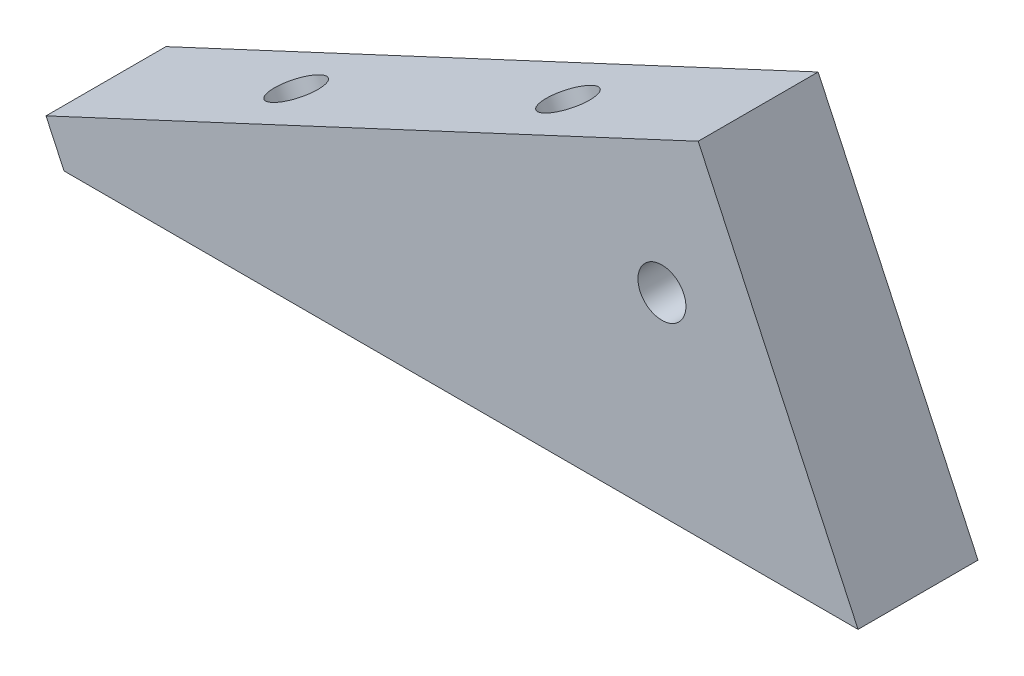
SolidWorks part; units mm, degrees
ref_plane "Front Plane" through (0, 0, 0) normal (0, 0, 1) x (1, 0, 0)
ref_plane "Top Plane" through (0, 0, 0) normal (0, 1, 0) x (1, 0, 0)
ref_plane "Right Plane" through (0, 0, 0) normal (1, 0, 0) x (0, 0, -1)
sketch "Sketch1" plane through (0, 0, 0) normal (0, 0, 1) x (1, 0, 0)
  line L0 (121.4984, 0.0035) -> (108.169, 28.5884)
  line L1 (-85.1981, -61.5801) -> (277.3251, 107.4672) construction
  line L2 (108.169, 28.5884) -> (53.7905, 3.2313)
  line L3 (53.7905, 3.2313) -> (55.2957, 0.0035)
  line L4 (55.2957, 0.0035) -> (121.4984, 0.0035)
  dimension "D1" = 60
  dimension "D2" = 31.54
extrude "Boss-Extrude1" add sketch "Sketch1" against normal blind 10
sketch "Sketch2" plane through (8.3697, -17.9488, 0) normal (-0.4226, 0.9063, 0) x (0.9063, 0.4226, 0)
  line L0 (50.1164, 5) -> (110.1164, 5) construction
  line L1 (50.1164, 10) -> (50.1164, 0) construction
  line L2 (110.1164, 10) -> (110.1164, 0) construction
  line L3 (80.1164, 10) -> (80.1164, 0) construction
  line L4 (92.6164, 0.9585) -> (96.1164, 2.9793)
  line L5 (96.1164, 2.9793) -> (96.1164, 7.0207)
  line L6 (96.1164, 7.0207) -> (92.6164, 9.0415)
  line L7 (92.6164, 9.0415) -> (89.1164, 7.0207)
  line L8 (89.1164, 7.0207) -> (89.1164, 2.9793)
  line L9 (89.1164, 2.9793) -> (92.6164, 0.9585)
  line L10 (110.1164, 10) -> (50.1164, 10) construction
  line L11 (110.1164, 0) -> (50.1164, 0) construction
  line L12 (71.1164, 2.9793) -> (67.6164, 0.9585)
  line L13 (67.6164, 0.9585) -> (64.1164, 2.9793)
  line L14 (71.1164, 7.0207) -> (71.1164, 2.9793)
  line L15 (67.6164, 9.0415) -> (71.1164, 7.0207)
  line L16 (64.1164, 7.0207) -> (67.6164, 9.0415)
  line L17 (64.1164, 2.9793) -> (64.1164, 7.0207)
  circle A0 centre (92.6164, 5) radius 3.5 construction
  circle A1 centre (92.6164, 5) radius 2
  circle A2 centre (67.6164, 5) radius 3.5 construction
  circle A3 centre (67.6164, 5) radius 2
  dimension "D3" = 4
  dimension "D1" = 17.5
  dimension "D2" = 7
extrude "Cut-Extrude1" cut sketch "Sketch2" against normal through all contours A3 | A1 region at (92.3086, 21.1926, -5) region at (69.6509, 10.6271, -5)
extrude "Cut-Extrude2" cut sketch "Sketch2<3>" against normal through all from offset 4 offset against normal yes
sketch "Sketch2<3>" plane through (8.3697, -17.9488, 0) normal (-0.4226, 0.9063, 0) x (0.9063, 0.4226, 0) same geometry as "Sketch2"
sketch "Sketch3" plane through (0, 0.0035, 0) normal (0, -1, 0) x (1, 0, 0)
  line L0 (121.4984, -5) -> (55.2957, -5) construction
  line L1 (121.4984, -10) -> (121.4984, 0) construction
  line L2 (55.2957, -10) -> (55.2957, 0) construction
  circle A0 centre (88.397, -5) radius 2
  circle A1 centre (113.9984, -5) radius 2
  dimension "D1" = 4
  dimension "D2" = 4
  dimension "D3" = 7.5
extrude "Cut-Extrude3" cut sketch "Sketch3" against normal blind 10
sketch "Sketch4" plane through (0, 0, 0) normal (0, 0, 1) x (1, 0, 0)
  line L0 (121.4984, 0.0035) -> (108.169, 28.5884) construction
  line L1 (109.1708, 15.7922) -> (107.4628, 19.455)
  line L2 (107.4628, 19.455) -> (103.4367, 19.8072)
  line L3 (103.4367, 19.8072) -> (101.1187, 16.4966)
  line L4 (101.1187, 16.4966) -> (102.8266, 12.8338)
  line L5 (102.8266, 12.8338) -> (106.8527, 12.4816)
  line L6 (106.8527, 12.4816) -> (109.1708, 15.7922)
  line L7 (108.169, 28.5884) -> (53.7905, 3.2313) construction
  circle A0 centre (105.1447, 16.1444) radius 2
  circle A1 centre (105.1447, 16.1444) radius 3.5 construction
  dimension "D4" = 4
  dimension "D1" = 8
  dimension "D2" = 10
  dimension "D3" = 7
  dimension "D5" = 0
extrude "Cut-Extrude4" cut sketch "Sketch4" against normal blind 10 contours A0 region at (105.1447, 16.1444, 0)
extrude "Cut-Extrude5" cut sketch "Sketch4<3>" along normal blind 5 from surface starting at face at (107.1447, 16.1444, -10)
sketch "Sketch4<3>" plane through (0, 0, 0) normal (0, 0, 1) x (1, 0, 0) same geometry as "Sketch4"
